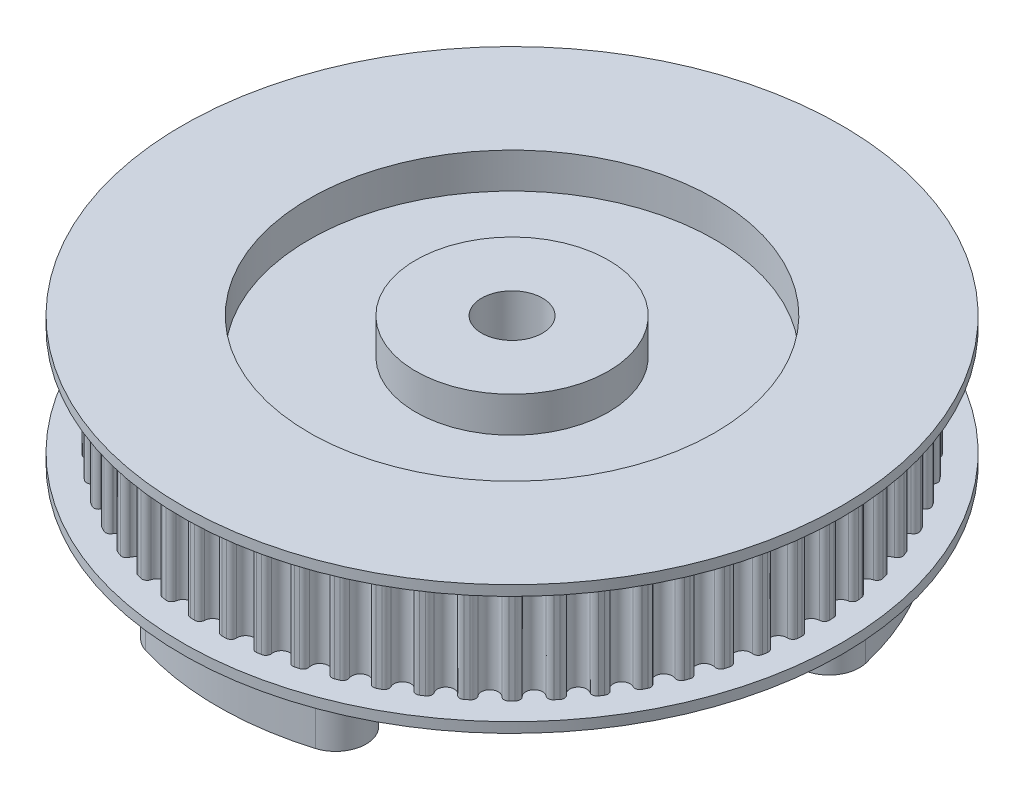
SolidWorks part; units mm, degrees
ref_plane "Front plan" through (0, 0, 0) normal (0, 0, 1) x (1, 0, 0)
ref_plane "Top plan" through (0, 0, 0) normal (0, 1, 0) x (1, 0, 0)
ref_plane "Right plan" through (0, 0, 0) normal (1, 0, 0) x (0, 0, -1)
sketch "Skica2" plane through (0, 0, 0) normal (0, 0, 1) x (1, 0, 0)
  line L1 (3, 3.8) -> (3, -8.9)
  line L3 (0, -9) -> (0, 9) construction
  line L7 (32.5, 2.8) -> (30, 2.8)
  line L8 (30, 2.8) -> (30, -7.9)
  line L9 (32.5, 2.8) -> (32.5, 3.8)
  line L12 (32.5, -8.9) -> (4, -8.9)
  line L13 (32.5, 3.8) -> (9, 3.8)
  line L14 (32.5, -8.9) -> (32.5, -7.9)
  line L15 (30, -7.9) -> (32.5, -7.9)
  line L17 (9, 3.8) -> (3, 3.8)
  line L18 (4, -8.9) -> (3, -8.9)
  point P7 (0, 0)
  dimension "D6" = 65
  dimension "D3" = 60
  dimension "D1" = 6
  dimension "D2" = 12.7
  dimension "D4" = 1
revolve "Revolute" add sketch "Skica2" angle 360 about L3 region at (16.712, -2.55, 0)
sketch "Sketch2" plane through (0, 2.8, 0) normal (0, -1, 0) x (1, 0, 0)
  line L0 (0, 0) -> (0, 29.5189) construction
  line L1 (0, 0) -> (10.1159, 28.243) construction
  line L3 (0, 0) -> (-2.1349, 29.9239) construction
  circle A1 centre (0, 0) radius 28.6829 construction
  circle A2 centre (0, 0) radius 29.5 construction
  arc A3 (-0.8354, 29.4882) -> (0.8354, 29.4882) centre (0, 29.5189) ccw
  arc A7 (-1.3577, 29.9693) -> (-2.1349, 29.9239) centre (0, 0) ccw
  arc A8 (0, 31.4637) -> (2.1349, 29.9239) centre (0.5632, 29.9947) cw
  circle A9 centre (0, 0) radius 30 construction
  arc A10 (1.3577, 29.9693) -> (2.1349, 29.9239) centre (0, 0) cw
  arc A11 (1.3577, 29.9693) -> (0.8354, 29.4882) centre (1.3351, 29.4698) ccw
  arc A12 (0, 31.4637) -> (-2.1349, 29.9239) centre (-0.5632, 29.9947) ccw
  arc A13 (-1.3577, 29.9693) -> (-0.8354, 29.4882) centre (-1.3351, 29.4698) cw
  dimension "D2" = 1
  dimension "D4" = 0.836
  dimension "D6" = 60
  dimension "D3" = 1.5733
  dimension "D1" = 0.5
extrude "Cut-Extrude3" cut sketch "Sketch2" along normal up to surface (10.7 mm away) up to face at (32.5, -7.9, 0)
pattern_circular "CirPattern1" count 60 over 360 about axis through (0, -9, 0) along (0, -1, 0) of "Cut-Extrude3"
sketch "Sketch4" plane through (0, -8.9, 0) normal (0, -1, 0) x (1, 0, 0)
  circle A0 centre (0, 0) radius 20
  circle A1 centre (0, 0) radius 9.5
  dimension "D1" = 40
  dimension "D2" = 19
extrude "Cut-Extrude4" cut sketch "Sketch4" against normal blind 3.5
ref_plane "Plane1" through (0, -2.55, 0) normal (0, -1, 0) x (-1, 0, 0)
mirror "Mirror1" about plane through (0, -2.55, 0) normal (0, -1, 0) of "Cut-Extrude4"
sketch "Sketch5" plane through (0, -8.9, 0) normal (0, -1, 0) x (1, 0, 0)
  arc A0 (-7.5, 24.8948) -> (7.5, 24.8948) centre (0, 0) cw construction
  arc A1 (8.3654, 27.7673) -> (-8.3654, 27.7673) centre (0, 0) ccw
  arc A2 (6.6346, 22.0223) -> (-6.6346, 22.0223) centre (0, 0) ccw
  arc A3 (6.6346, 22.0223) -> (8.3654, 27.7673) centre (7.5, 24.8948) ccw
  arc A4 (-8.3654, 27.7673) -> (-6.6346, 22.0223) centre (-7.5, 24.8948) ccw
  point P3 (0, 26)
  point P15 (0, 29)
  dimension "D1" = 3
  dimension "D3" = 15
  dimension "D2" = 26
extrude "Boss-Extrude1" add sketch "Sketch5" along normal blind 6.2
pattern_circular "CirPattern2" count 3 over 240 about axis through (0, -8.9, 0) along (0, -1, 0) of "Boss-Extrude1"
sketch "Sketch6" plane through (0, 0.3, 0) normal (0, 1, 0) x (1, 0, 0)
  circle A0 centre (0, 0) radius 20
  circle A1 centre (0, 0) radius 9.5
equation "\"`\"=2"
equation "\"D6@Sketch2\"= \"D3@Skica2\""
